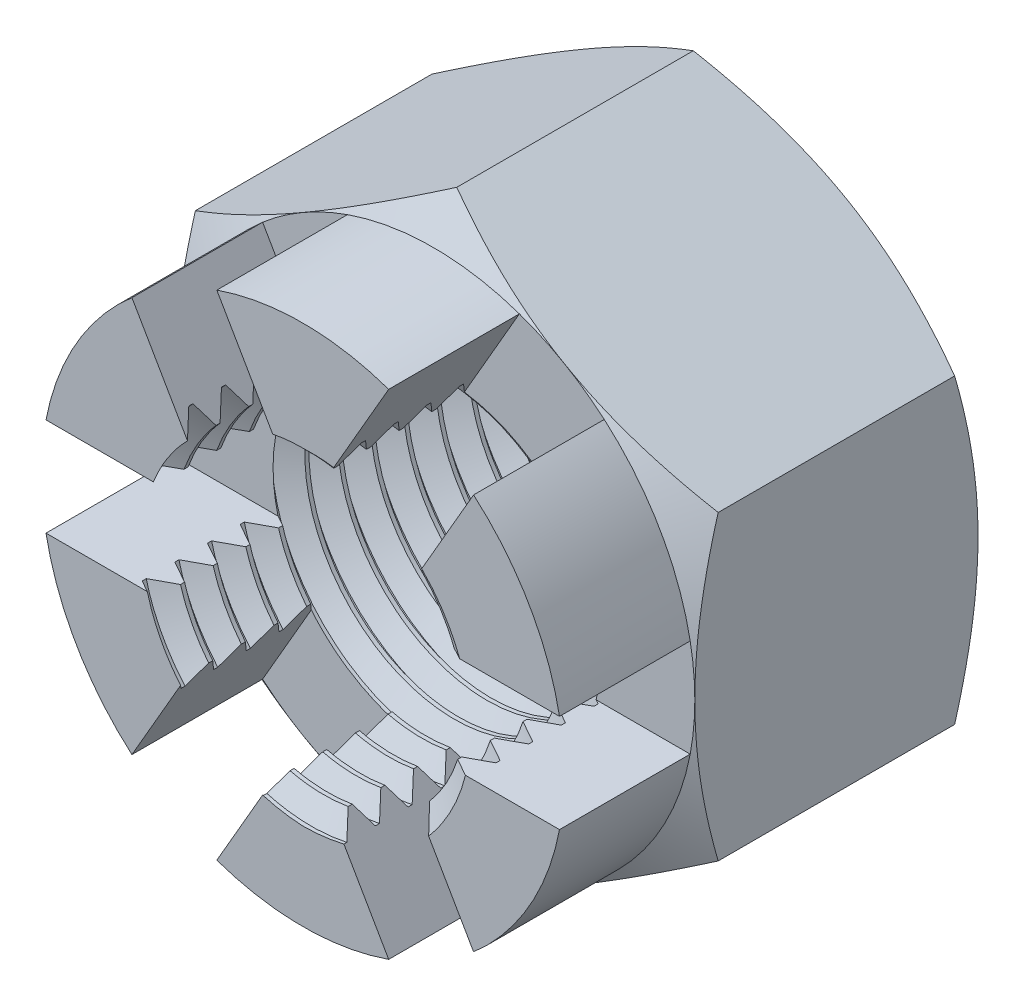
SolidWorks part; units mm, degrees
note: '?' marks a value the reader was unsure of.
ref_plane "Front Plane" through (0, 0, 0) normal (0, 0, 1) x (1, 0, 0)
ref_plane "Top Plane" through (0, 0, 0) normal (0, 1, 0) x (1, 0, 0)
ref_plane "Right Plane" through (0, 0, 0) normal (1, 0, 0) x (0, 0, -1)
sketch "Sketch1" plane through (0, 0, 0) normal (0, 0, 1) x (1, 0, 0)
  line L1 (0, 13.8564) -> (-12, 6.9282)
  line L2 (-12, 6.9282) -> (-12, -6.9282)
  line L3 (-12, -6.9282) -> (0, -13.8564)
  line L4 (0, -13.8564) -> (12, -6.9282)
  line L5 (12, -6.9282) -> (12, 6.9282)
  line L6 (12, 6.9282) -> (0, 13.8564)
  circle A0 centre (0, 0) radius 12 construction
  dimension "Hex" = 24
extrude "Extrude1" add sketch "Sketch1" against normal blind 19
sketch "Sketch2" plane through (0, 0, 0) normal (0, 0, 1) x (1, 0, 0)
  circle A0 centre (0, 0) radius 12 construction
  circle A1 centre (0, 0) radius 12
sketch "Sketch3" plane through (0, 0, -19) normal (0, 0, -1) x (-1, 0, 0)
  circle A1 centre (0, 0) radius 12
  circle A2 centre (0, 0) radius 12
  dimension "D1" = 0
extrude "Cut-Extrude2" cut sketch "Sketch3" against normal through all draft 60 flip side to cut
sketch "Sketch4" plane through (0, 0, 0) normal (0, 0, 1) x (1, 0, 0)
  circle A0 centre (0, 0) radius 8
  dimension "Thread Dia" = 16
extrude "Cut-Extrude3" cut sketch "Sketch4" against normal through all
sketch "Sketch5" plane through (0, 0, 0) normal (0, 0, 1) x (1, 0, 0)
  circle A0 centre (0, 0) radius 8 construction
  circle A1 centre (0, 0) radius 8
sketch "Sketch9" plane through (0, 0, 0) normal (1, 0, 0) x (0, 0, -1)
  line L0 (-0.75, 8) -> (-0.5625, 8)
  line L1 (-0.5625, 8) -> (0, 7.0257)
  line L2 (-0.75, 8) -> (-1.3125, 7.0257)
  line L3 (-1.3125, 7.0257) -> (0, 7.0257)
  line L4 (-0.6563, 8) -> (-0.6563, 7.0257) construction
  line L5 (-1.0313, 7.5129) -> (-0.2813, 7.5129) construction
  line L7 (0, 7.0257) -> (0, 8) construction
  line L8 (0, 8) -> (0, -8) construction
  dimension "D1" = 0.1875
  dimension "D2" = 0.75
  dimension "D3" = 60
sketch "Sketch13" plane through (0, 0, 0) normal (0, 0, 1) x (1, 0, 0)
  line L0 (-1.9486, 1.125) -> (1.9486, -1.125)
  line L1 (-1.9486, 1.125) -> (4.0514, 11.5173)
  line L2 (1.9486, -1.125) -> (7.9486, 9.2673)
  line L3 (4.0514, 11.5173) -> (7.9486, 9.2673)
  line L5 (12, 6.9282) -> (0, 13.8564) construction
  dimension "slot width" = 4.5
extrude "Cut-Extrude8" cut sketch "Sketch13" against normal blind 6
sketch "Sketch14" plane through (0, 0, -6) normal (0, 0, 1) x (1, 0, 0)
  circle A0 centre (0, 0) radius 12 construction
  circle A1 centre (0, 0) radius 12
extrude "Cut-Extrude9" cut sketch "Sketch14" against normal through all draft 60 flip side to cut
sketch "Sketch15" plane through (0, 0, 0) normal (0, 0, 1) x (1, 0, 0)
  circle A0 centre (0, 0) radius 12 construction
  circle A1 centre (0, 0) radius 12
extrude "Cut-Extrude10" cut sketch "Sketch15" against normal up to surface (6 mm away) flip side to cut up to face at (5.1358, 8.8954, -6)
pattern_circular "CirPattern2" count 6 over 360 about axis through (0, 0, 0) along (0, 0, 1) of "Cut-Extrude8"
sketch "ref" plane through (0, 0, 0) normal (0, 0, 1) x (1, 0, 0)
  line L0 (12, 2.25) -> (12, -2.25) construction
  line L1 (4.0514, 11.5173) -> (7.9486, 9.2673) construction
  point P4 (12, 0)
curve "Helix/Spiral1" pitch 1.5 height 20.5 turns 13.6667 parameters "pitch"=1.5
sketch "Sketch12" plane through (0, 0, 0) normal (0, 0, 1) x (1, 0, 0)
  circle A0 centre (0, 0) radius 7.0257
  circle A1 centre (0, 0) radius 8 construction
  circle A2 centre (0, 0) radius 8
extrude "Extrude2" add sketch "Sketch12" against normal up to surface (19 mm away) separate body up to face at (8, 0, -19)
sweep "Cut-Sweep1" cut profiles "Sketch9" path "Helix/Spiral1"
sketch "Sketch16" plane through (0, 0, -19) normal (0, 0, -1) x (-1, 0, 0)
  circle A0 centre (0, 0) radius 8.1
  circle A1 centre (0, 0) radius 8
  circle A2 centre (0, 0) radius 8
  dimension "D1" = 0
  dimension "D2" = 0.1
extrude "Boss-Extrude1" add sketch "Sketch16" against normal blind 0.1
sketch "Sketch17" plane through (0, 0, 0) normal (0, 0, 1) x (1, 0, 0)
  line L4 (-1.9486, 1.125) -> (1.9486, -1.125)
  line L5 (1.9486, -1.125) -> (7.9486, 9.2673)
  line L6 (7.9486, 9.2673) -> (4.0514, 11.5173)
  line L7 (4.0514, 11.5173) -> (-1.9486, 1.125)
  line L8 (-1.9486, 1.125) -> (1.9486, -1.125)
  line L9 (1.9486, -1.125) -> (7.9486, 9.2673)
  line L10 (7.9486, 9.2673) -> (4.0514, 11.5173)
  line L11 (4.0514, 11.5173) -> (-1.9486, 1.125)
  dimension "D1" = 0
extrude "Cut-Extrude11" cut sketch "Sketch17" against normal up to surface (6 mm away) up to face at (5.1358, 8.8954, -6)
pattern_circular "CirPattern3" count 6 over 360 about axis through (0, 0, -41.6274) along (0, 0, 1) of "Cut-Extrude11"
ref_axis "Center Axis 1" through (0, 0, -17.6743) along (0, 0, 1)?
equation "\"D2@Sketch9\" = \"pitch@Helix/Spiral1\"*.5"
equation "\"D3@Helix/Spiral1\" = \"pitch@Helix/Spiral1\"+\"Height@Extrude1\""
equation "\"D1@Sketch9\" = \"pitch@Helix/Spiral1\"*.125"
